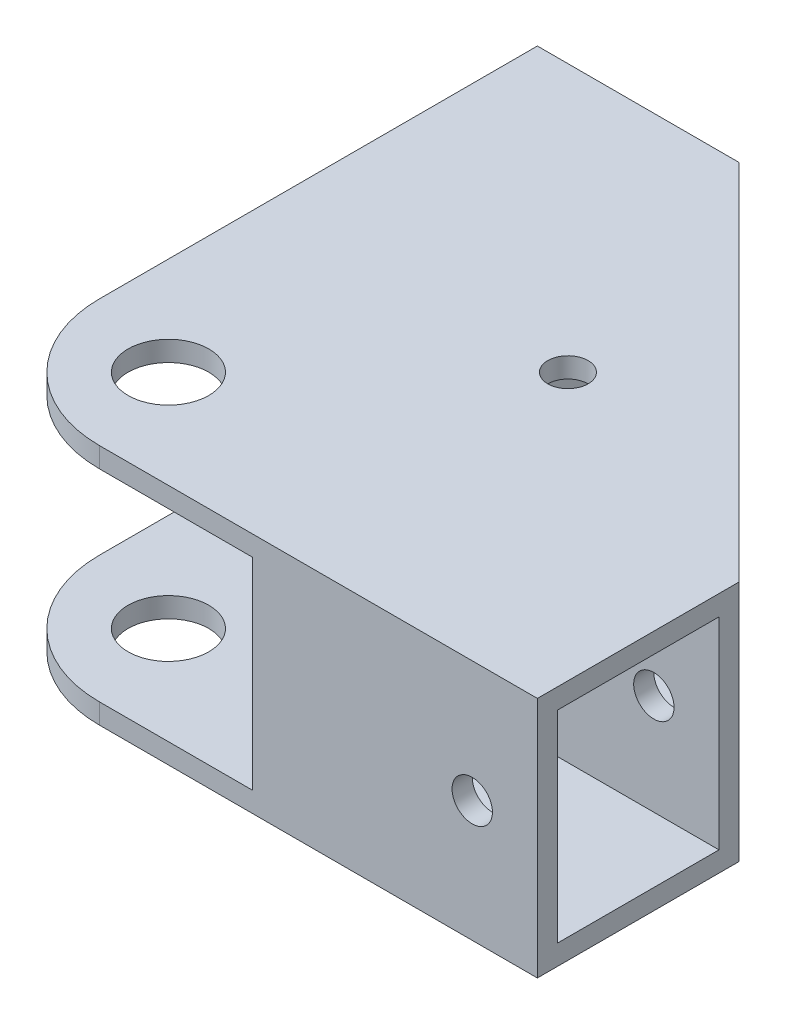
SolidWorks part; units mm, degrees
material "6061-T6 (SS)"
ref_plane "Front Plane" through (0, 0, 0) normal (0, 0, 1) x (1, 0, 0)
ref_plane "Top Plane" through (0, 0, 0) normal (0, 1, 0) x (1, 0, 0)
ref_plane "Right Plane" through (0, 0, 0) normal (1, 0, 0) x (0, 0, -1)
sketch "Sketch1" plane through (0, 0, 0) normal (0, 1, 0) x (1, 0, 0)
  line L0 (0, 0) -> (-88.9, 0)
  line L1 (-88.9, 0) -> (-88.9, 88.9)
  line L2 (-88.9, 88.9) -> (-57.15, 88.9)
  line L3 (-57.15, 88.9) -> (-57.15, 31.75)
  line L4 (-57.15, 31.75) -> (0, 31.75)
  line L5 (0, 31.75) -> (0, 0)
  point P6 (0, 88.9)
  dimension "D1" = 57.15
  dimension "D2" = 31.75
extrude "Boss-Extrude1" add sketch "Sketch1" along normal blind 38.1
sketch "Sketch2" plane through (0, 0, 0) normal (1, 0, 0) x (0, 0, -1)
  line L0 (31.75, 0) -> (0, 38.1) construction
  line L23 (3.175, 34.925) -> (3.175, 3.175)
  line L24 (3.175, 3.175) -> (28.575, 3.175)
  line L25 (28.575, 3.175) -> (28.575, 34.925)
  line L26 (28.575, 34.925) -> (3.175, 34.925)
  line L27 (3.175, 34.925) -> (3.175, 3.175)
  line L28 (3.175, 3.175) -> (28.575, 3.175)
  line L29 (28.575, 3.175) -> (28.575, 34.925)
  line L30 (28.575, 34.925) -> (3.175, 34.925)
  dimension "D1" = 3.175
extrude "Cut-Extrude1" cut sketch "Sketch2" against normal up to surface (88.9 mm away) up to face at (-88.9, 19.05, -44.45)
sketch "Sketch3" plane through (0, 0, -88.9) normal (0, 0, -1) x (-1, 0, 0)
  line L0 (57.15, 0) -> (88.9, 38.1) construction
  line L17 (60.325, 3.175) -> (85.725, 3.175)
  line L18 (60.325, 34.925) -> (60.325, 3.175)
  line L19 (85.725, 3.175) -> (85.725, 34.925)
  line L20 (85.725, 34.925) -> (60.325, 34.925)
  line L21 (60.325, 3.175) -> (85.725, 3.175)
  line L22 (60.325, 34.925) -> (60.325, 3.175)
  line L23 (85.725, 3.175) -> (85.725, 34.925)
  line L24 (85.725, 34.925) -> (60.325, 34.925)
  dimension "D1" = 3.175
extrude "Cut-Extrude2" cut sketch "Sketch3" against normal up to surface (88.9 mm away) up to face at (-44.45, 19.05, 0)
ref_plane "Plane1" through (0, 0, 0) normal (0.7071, 0, -0.7071) x (-0.7071, 0, -0.7071)
sketch "Sketch4" plane through (0, 0, 0) normal (0.7071, 0, -0.7071) x (-0.7071, 0, -0.7071)
  line L0 (125.7236, 38.1) -> (62.8618, 38.1) construction
  line L1 (100.3618, 34.925) -> (25.3618, 34.925)
  line L2 (100.3618, 34.925) -> (100.3618, 3.175)
  line L3 (100.3618, 3.175) -> (25.3618, 3.175)
  line L4 (25.3618, 34.925) -> (25.3618, 3.175)
  line L5 (100.3618, 34.925) -> (100.3618, 38.1) construction
  line L6 (100.3618, 3.175) -> (100.3618, 0) construction
  line L7 (125.7236, 0) -> (62.8618, 0) construction
  point P4 (62.8618, 34.925)
  dimension "D1" = 3.175
  dimension "D2" = 75
extrude "Cut-Extrude3" cut sketch "Sketch4" along normal blind 28.575 from vertex starting at point (-88.9, 38.1, 0)
fillet "Fillet4" radius 20 2 edges at (-88.9, 1.5875, 0) (-88.9, 36.5125, 0)
sketch "Sketch8" plane through (0, 34.925, 0) normal (0, -1, 0) x (1, 0, 0)
  line L0 (-83.0421, -5.8579) -> (-57.15, -31.75) construction
  line L4 (-57.15, -88.9) -> (0, -31.75) construction
  circle A0 centre (-73.4763, -15.4237) radius 6.35
  arc A1 (-68.9, 0) -> (-88.9, -20) centre (-68.9, -20) ccw construction
  point P13 (-73.4763, -15.4237)
  dimension "D1" = 12.7
  dimension "D2" = 63.5
extrude "Cut-Extrude8" cut sketch "Sketch8" against normal through all both and the other way through all
ref_plane "Plane2" through (-44.45, 0, -44.45) normal (0.7071, 0, 0.7071) x (0.7071, 0, -0.7071)
sketch "Sketch29" plane through (0, 38.1, 0) normal (0, 1, 0) x (1, 0, 0)
  line L0 (-57.15, 88.9) -> (0, 31.75)
  line L1 (-57.15, 88.9) -> (-57.15, 31.75)
  line L2 (-57.15, 31.75) -> (0, 31.75)
extrude "Boss-Extrude2" add sketch "Sketch29" against normal blind 3.175
sketch "Sketch35" plane through (-88.9, 0, 0) normal (-1, 0, 0) x (0, 0, 1)
  line L0 (-88.9, 38.1) -> (-88.9, 0) construction
  line L1 (-88.9, 38.1) -> (-20, 38.1) construction
  circle A0 centre (-78.65, 19.05) radius 3.175
  dimension "D1" = 10.25
  dimension "D3" = 6.35
  dimension "D2" = 19.05
extrude "Cut-Extrude10" cut sketch "Sketch35" against normal up to surface (31.75 mm away) up to face at (-57.15, 17.4625, -60.325)
sketch "Sketch36" plane through (0, 0, 0) normal (0, 0, 1) x (1, 0, 0)
  line L0 (0, 38.1) -> (0, 0) construction
  line L1 (-68.9, 38.1) -> (0, 38.1) construction
  circle A0 centre (-10.25, 19.05) radius 3.175
  dimension "D1" = 6.35
  dimension "D2" = 10.25
  dimension "D3" = 19.05
extrude "Cut-Extrude11" cut sketch "Sketch36" against normal up to surface (31.75 mm away) up to face at (-28.575, 17.4625, -31.75)
ref_plane "Plane5" through (0, 19.05, 0) normal (0, -1, 0) x (-1, 0, 0)
mirror "Mirror1" about plane through (0, 19.05, 0) normal (0, -1, 0) of "Boss-Extrude2"
fillet "Fillet8" radius 5 2 edges at (-60.325, 19.05, -28.575) (-57.15, 19.05, -31.75)
chamfer "Chamfer1" distance 10 angle 45 2 edges at (-51.6638, 19.05, -3.175) (-85.725, 19.05, -37.2362) first distance on face at (-7.075, 19.05, -3.175) first distance on face at (-85.725, 19.05, -75.475)
sketch "Sketch37" plane through (0, 0, 0) normal (0, -1, 0) x (1, 0, 0)
  line L2 (0, -31.75) -> (-57.15, -88.9) construction
  line L3 (-55.5158, -33.3842) -> (-28.575, -60.325) construction
  circle A2 centre (-42.0454, -46.8546) radius 3.175
  dimension "D1" = 38.1
  dimension "D3" = 6.35
  dimension "D2" = 40.4112
extrude "Cut-Extrude12" cut sketch "Sketch37" against normal up to surface (38.1 mm away) up to face at (-51.332, 38.1, -37.568)
